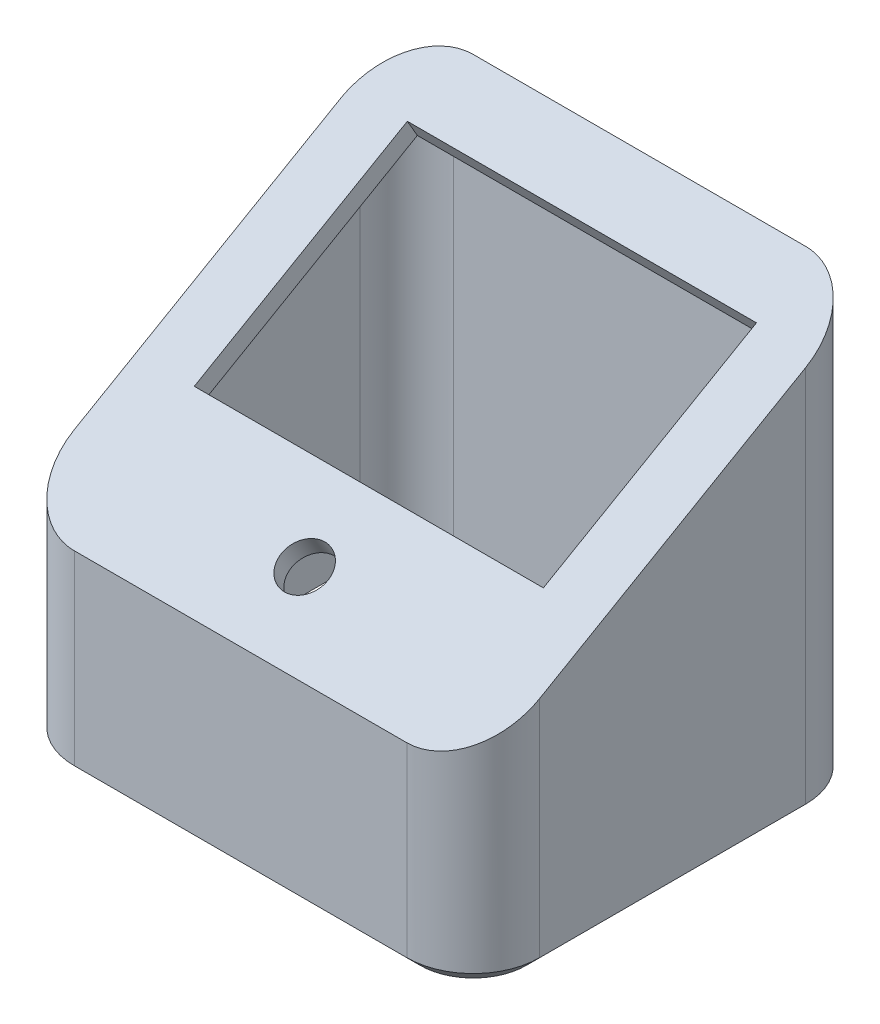
SolidWorks part; units mm, degrees
ref_plane "Front Plane" through (0, 0, 0) normal (0, 0, 1) x (1, 0, 0)
ref_plane "Top Plane" through (0, 0, 0) normal (0, 1, 0) x (1, 0, 0)
ref_plane "Right Plane" through (0, 0, 0) normal (1, 0, 0) x (0, 0, -1)
sketch "Sketch1" plane through (0, 0, 0) normal (0, 1, 0) x (1, 0, 0)
  line L1 (-35, -30) -> (35, -30)
  line L2 (-35, -30) -> (-35, 30)
  line L3 (-35, 30) -> (35, 30)
  line L4 (35, -30) -> (35, 30)
  line L5 (-35, -30) -> (35, 30) construction
  line L6 (-35, 30) -> (35, -30) construction
  point P0 (0, 0)
  dimension "D1" = 70
  dimension "D2" = 60
extrude "Boss-Extrude1" add sketch "Sketch1" along normal blind 30 contours L2 L3 L4 L1
sketch "Sketch2" plane through (35, 0, 0) normal (1, 0, 0) x (0, 0, -1)
  line L0 (-30, 30) -> (30, 30) construction
  line L1 (-30, 30) -> (30, 30)
  line L2 (30, 30) -> (30, 64.641)
  line L3 (30, 64.641) -> (-30, 30)
  dimension "D1" = 30
extrude "Boss-Extrude2" add sketch "Sketch2" against normal up to surface (70 mm away) up to face at (-35, 15, 0)
fillet "Fillet1" radius 10 4 edges at (35, 32.3205, -30) (35, 15, 30) (-35, 15, 30) (-35, 32.3205, -30)
shell "Shell1" thickness 3 removed face at (0, 0, 0)
sketch "Sketch3" plane through (0, 35.4904, 20.4904) normal (0, 0.866, 0.5) x (1, 0, 0)
  line L0 (0, -1000) -> (0, 49000) construction
  line L1 (-25, 58.3013) -> (25, 58.3013) construction
  line L2 (-26.25, 48.3013) -> (26.25, 48.3013)
  line L3 (-26.25, 48.3013) -> (-26.25, 11.3013)
  line L4 (-26.25, 11.3013) -> (26.25, 11.3013)
  line L5 (26.25, 48.3013) -> (26.25, 11.3013)
  line L6 (-26.25, 48.3013) -> (26.25, 11.3013) construction
  line L7 (-26.25, 11.3013) -> (26.25, 48.3013) construction
  point P1 (0, 29.8013)
  dimension "D1" = 37
  dimension "D2" = 52.5
  dimension "D3" = 10
extrude "Cut-Extrude1" cut sketch "Sketch3" against normal up to surface (3 mm away) up to face at (0, 43.8564, 0)
chamfer "Chamfer2" distance 2 angle 45 8 edges at (-35, 0, 0) (-32.0711, 0, 27.0711) (-32.0711, 0, -27.0711) (0, 0, 30) (0, 0, -30) (32.0711, 0, 27.0711) (32.0711, 0, -27.0711) (35, 0, 0)
sketch "Sketch4" plane through (0, 35.4904, 20.4904) normal (0, 0.866, 0.5) x (1, 0, 0)
  line L0 (0, -1000) -> (0, 49000) construction
  line L4 (-26.25, 11.3013) -> (26.25, 11.3013) construction
  line L5 (-26.25, 11.3013) -> (26.25, 11.3013) construction
  line L6 (-25, -10.9808) -> (25, -10.9808) construction
  line L7 (-25, -10.9808) -> (25, -10.9808) construction
  line L8 (0, 11.3013) -> (0, -10.9808) construction
  circle A0 centre (0, 0.1603) radius 3.5
  point P5 (0, 0.1603)
  point P12 (0, 0)
  point P13 (0, 0)
  dimension "D1" = 7
extrude "Cut-Extrude2" cut sketch "Sketch4" against normal up to surface (3 mm away) contours A0 up to face at (0, 47.7929, -6.8183)
